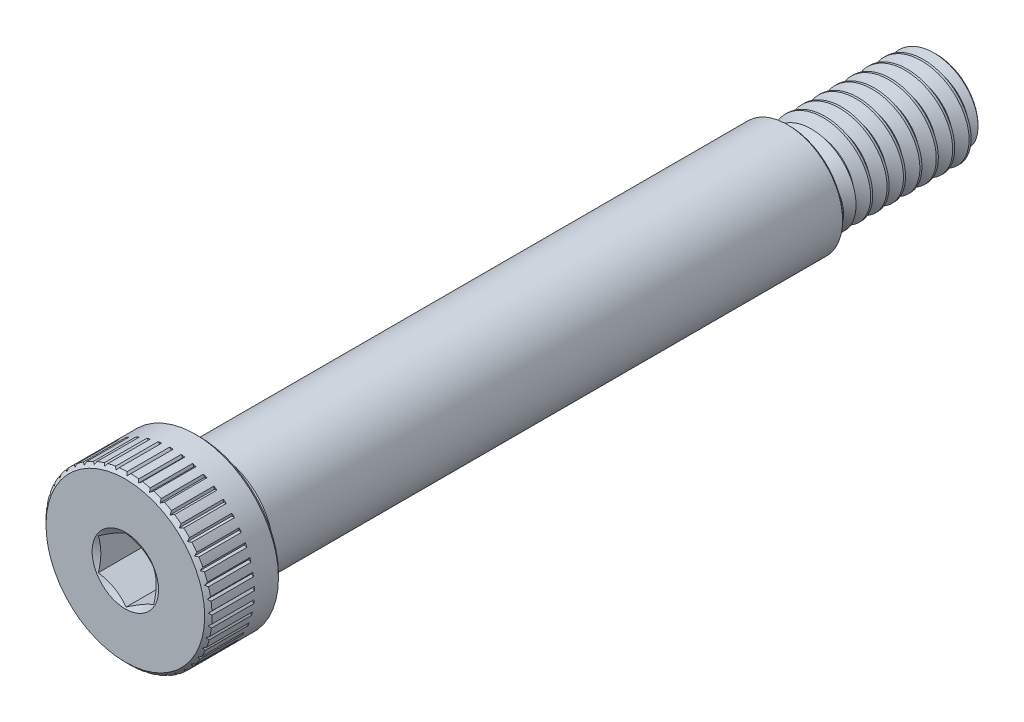
SolidWorks part; units mm, degrees
ref_plane "Front Plane" through (0, 0, 0) normal (0, 0, 1) x (1, 0, 0)
ref_plane "Top Plane" through (0, 0, 0) normal (0, 1, 0) x (1, 0, 0)
ref_plane "Right Plane" through (0, 0, 0) normal (1, 0, 0) x (0, 0, -1)
sketch "Sketch1" plane through (0, 0, 0) normal (1, 0, 0) x (0, 0, -1)
  line L0 (-50.8, 7.1437) -> (-50.8, -7.1437) construction
  line L1 (-57.15, 0) -> (12.7, 0) construction
  line L2 (12.7, 3.9751) -> (12.7, -3.9751) construction
  line L3 (-57.15, 2.3813) -> (-57.15, -2.3813) construction
  line L4 (0, 4.7625) -> (0, -4.7625) construction
  line L5 (12.6118, 4.1279) -> (13.3174, 2.9058) construction
  line L6 (13.3174, 2.9058) -> (14.0229, 4.1279) construction
  line L7 (14.0229, 4.1279) -> (12.6118, 4.1279) construction
  line L8 (12.7, 3.9751) -> (13.9347, 3.9751) construction
  line L9 (13.2292, 3.0586) -> (13.4056, 3.0586) construction
  line L10 (13.3174, 3.0586) -> (13.3174, 2.9058) construction
  line L11 (13.3174, 3.9751) -> (13.3174, 4.1279) construction
  point P6 (-50.8, 0)
  point P7 (0, 0)
  point P15 (9.1722, -3.9751)
  point P23 (-5.08, -4.7625)
  point P24 (-45.72, -4.7625)
  point P25 (-57.15, 7.1437)
  point P26 (12.7, 4.7625)
  point P30 (-50.8, -4.7625)
  point P31 (-50.8, 4.7625)
  dimension "Drive Size" = 4.7625
  dimension "Head Diameter" = 14.2875
  dimension "Head Height" = 6.35
  dimension "Screw Size Decimal Equivalent" = 7.9502
  dimension "Shoulder Length" = 50.8
  dimension "Thread Length" = 12.7
  dimension "Thread Pitch" = 1.4111
  dimension "D1" = 0.1764
  dimension "Thread Note" = 3.5278
  dimension "Break Line 1" = 5.08
  dimension "Break Line 2" = 5.08
  dimension "Shoulder Diameter" = 9.525
sketch "Sketch2" plane through (0, 0, 0) normal (1, 0, 0) x (0, 0, -1)
  line L0 (-57.15, 0) -> (-57.15, 6.8263)
  line L1 (-57.15, 6.8263) -> (-56.8325, 7.1437)
  line L2 (-56.8325, 7.1437) -> (-51.1175, 7.1437)
  line L3 (-51.1175, 7.1437) -> (-50.8, 6.8263)
  line L4 (-50.8, 7.1437) -> (-50.8, -7.1437) construction
  line L5 (-50.8, 6.8263) -> (-50.8, 4.7625)
  line L6 (-49.1987, 4.7625) -> (-0.1969, 4.7625)
  line L7 (-0.1969, 4.7625) -> (0, 4.5656)
  line L8 (0, 4.7625) -> (0, -4.7625) construction
  line L9 (0, 4.5656) -> (0, 3.1594)
  line L10 (1.3458, 3.9751) -> (11.9944, 3.9751)
  line L11 (11.9944, 3.9751) -> (12.7, 3.2695)
  line L12 (12.7, 3.9751) -> (12.7, -3.9751) construction
  line L13 (12.7, 3.2695) -> (12.7, 0)
  line L14 (12.7, 0) -> (-57.15, 0)
  line L16 (1.3458, 3.9751) -> (0.8828, 2.9822)
  line L17 (0.8828, 2.9822) -> (0.1772, 2.9822)
  line L18 (13.3174, 3.0586) -> (13.3174, 2.9058) construction
  line L19 (-57.15, 2.3813) -> (-57.15, -2.3813) construction
  line L20 (13.3174, 3.9751) -> (13.3174, 3.0586) construction
  line L21 (12.7, 3.9751) -> (13.9347, 3.9751) construction
  line L22 (12.9646, 3.5168) -> (13.6701, 3.5168) construction
  line L23 (12.6118, 4.1279) -> (13.3174, 2.9058) construction
  line L24 (-50.8, 4.7625) -> (-50.6838, 4.3288)
  line L25 (-50.6838, 4.3288) -> (-49.4491, 4.3288)
  line L26 (-49.4491, 4.3288) -> (-49.1987, 4.7625)
  line L27 (-49.1987, 4.7625) -> (-49.1987, 4.3288) construction
  arc A2 (0.1772, 2.9822) -> (0, 3.1594) centre (0.1772, 3.1594) cw
  point P29 (13.3174, 2.9822)
  point P30 (13.3174, 3.5168)
  point P38 (-53.1812, 7.1437)
  point P45 (0, 2.9822)
  dimension "D1" = 45
  dimension "D2" = 0.3175
  dimension "D3" = 0.7056
  dimension "D4" = 0.1968
  dimension "D5" = 65
  dimension "D6" = 15
  dimension "D7" = 30
  dimension "D8" = 45
  dimension "D9" = 3.9688
revolve "Revolve2" add sketch "Sketch2" angle 360 about L1
sketch "Sketch3" plane through (0, 0, 57.15) normal (0, 0, 1) x (1, 0, 0)
  line L1 (2.3812, 1.3748) -> (0, 2.7496)
  line L2 (0, 2.7496) -> (-2.3812, 1.3748)
  line L3 (-2.3812, 1.3748) -> (-2.3812, -1.3748)
  line L4 (-2.3812, -1.3748) -> (0, -2.7496)
  line L5 (0, -2.7496) -> (2.3812, -1.3748)
  line L6 (2.3812, -1.3748) -> (2.3812, 1.3748)
  circle A0 centre (0, 0) radius 2.3813 construction
  circle A1 centre (0, 0) radius 7.1438 construction
extrude "Cut-Extrude1" cut sketch "Sketch3" against normal blind 3.9688
sketch "Sketch4" plane through (0, 0, 57.15) normal (0, 0, 1) x (1, 0, 0)
  circle A0 centre (0, 0) radius 2.8575
  dimension "D1" = 5.715
extrude "Cut-Extrude2" cut sketch "Sketch4" against normal through all draft 60
sketch "Sketch5" plane through (0, 0, 53.1812) normal (0, 0, 1) x (1, 0, 0)
  circle A0 centre (0, 0) radius 2.3813
  circle A1 centre (0, 0) radius 2.3813 construction
extrude "Cut-Extrude3" cut sketch "Sketch5" against normal through all draft 85
split "Split1" trim tools "Front Plane" bodies to split 107 resulting bodies 108 109
other "DeleteFace3" face at (3.9751, 0, -11.9944) face at (2.9822, 0, -0.8828) face at (2.9822, 0, -0.1772) face at (3.1594, 0, 0) and patch yes
sketch "Sketch6" plane through (0, 0, -12.7) normal (0, 0, -1) x (-1, 0, 0)
  circle A0 centre (0, 0) radius 3.9751
curve "Helix/Spiral1" pitch 1.4111 height 14.1111 radius 3.9751 centre (0, 0, -12.7) axis (0, 0, 1) start towards (0, 1, 0)
sketch "Sketch8" plane through (0, 0, 0) normal (1, 0, 0) x (0, 0, -1)
  line L0 (13.2292, 3.0586) -> (13.4056, 3.0586)
  line L1 (13.4056, 3.0586) -> (13.9788, 4.0515)
  line L2 (13.3174, 2.9058) -> (14.0229, 4.1279) construction
  line L3 (13.9788, 4.0515) -> (12.6559, 4.0515)
  line L4 (12.6118, 4.1279) -> (13.3174, 2.9058) construction
  line L5 (12.6559, 4.0515) -> (13.2292, 3.0586)
  line L6 (13.3174, 3.9751) -> (13.3174, 4.1279) construction
  point P12 (13.3174, 4.0515)
sweep "Cut-Sweep2" cut profiles "Sketch8" path "Helix/Spiral1" align with end faces yes
sketch "Sketch9" plane through (0, 0, 0) normal (1, 0, 0) x (0, 0, -1)
  line L2 (0, 4.5656) -> (0, 3.1594) construction
  line L4 (0.8828, 2.9822) -> (0.1772, 2.9822) construction
  line L5 (11.4543, 4.7625) -> (12.7, 3.5168)
  line L7 (0, 4.7625) -> (0, 3.1594)
  line L8 (2.6631, 4.7625) -> (0.8828, 2.9822)
  line L9 (0.8828, 2.9822) -> (0.1772, 2.9822)
  line L10 (0, 4.7625) -> (2.6631, 4.7625)
  line L11 (12.7, 4.7625) -> (12.7, 3.5168)
  line L12 (11.4543, 4.7625) -> (12.7, 4.7625)
  line L13 (12.7, 3.9751) -> (12.7, -3.9751) construction
  arc A0 (0, 3.1594) -> (0.1772, 2.9822) centre (0.1772, 3.1594) ccw construction
  arc A1 (0, 3.1594) -> (0.1772, 2.9822) centre (0.1772, 3.1594) ccw
  dimension "D1" = 45
  dimension "D2" = 45
revolve "Cut-Revolve3" cut sketch "Sketch9" angle 360 about L1
combine bodies "Combine1" operation type add bodies to combine 108 112
sketch "Sketch10" plane through (0, 0, 0) normal (0, 0, 1) x (1, 0, 0)
  line L0 (-0.1587, 7.1437) -> (0, 6.985)
  line L1 (0, 6.985) -> (0.1587, 7.1437)
  line L2 (0.1587, 7.1437) -> (-0.1587, 7.1437)
  dimension "D1" = 0.1588
extrude "Cut-Extrude4" cut sketch "Sketch10" along normal through all from vertex starting at point (0, 7.1437, 53.1812)
pattern_circular "CirPattern1" count 45 over 360 about axis through (0, 0, 57.15) along (0, 0, -1) of "Cut-Extrude4"
equation "\"D2@Sketch2\"=\"Head Height@Sketch1\"*.05"
equation "\"D3@Sketch2\"=\"Thread Pitch@Sketch1\"*.5"
equation "\"D1@Sketch1\"=\"Thread Pitch@Sketch1\"/8"
equation "\"Thread Note@Sketch1\"=\"Thread Pitch@Sketch1\"*2.5"
equation "\"Break Line 1@Sketch1\" = \"Shoulder Length@Sketch1\" * .1"
equation "\"Break Line 2@Sketch1\" = \"Break Line 1@Sketch1\""
equation "\"D4@Sketch2\"=(\"Shoulder Diameter@Sketch1\"-\"Screw Size Decimal Equivalent@Sketch1\")*.125"
equation "\"D1@Cut-Extrude1\"=\"Head Height@Sketch1\" * .625"
equation "\"D1@Sketch4\"=\"Drive Size@Sketch1\"*1.2"
equation "\"D3@Helix/Spiral1\"=\"thread length@sketch1\"+\"thread pitch@sketch1\""
equation "\"D4@Helix/Spiral1\"=\"thread pitch@sketch1\""
equation "\"D1@Sketch10\"=\"D2@Sketch2\"*.5"
equation "\"D9@Sketch2\"=\"Head Height@Sketch1\"*.625"
equation "\"D1@CirPattern1\"=\"Head Diameter@Sketch1\" / \"D1@Sketch10\"*.5"
